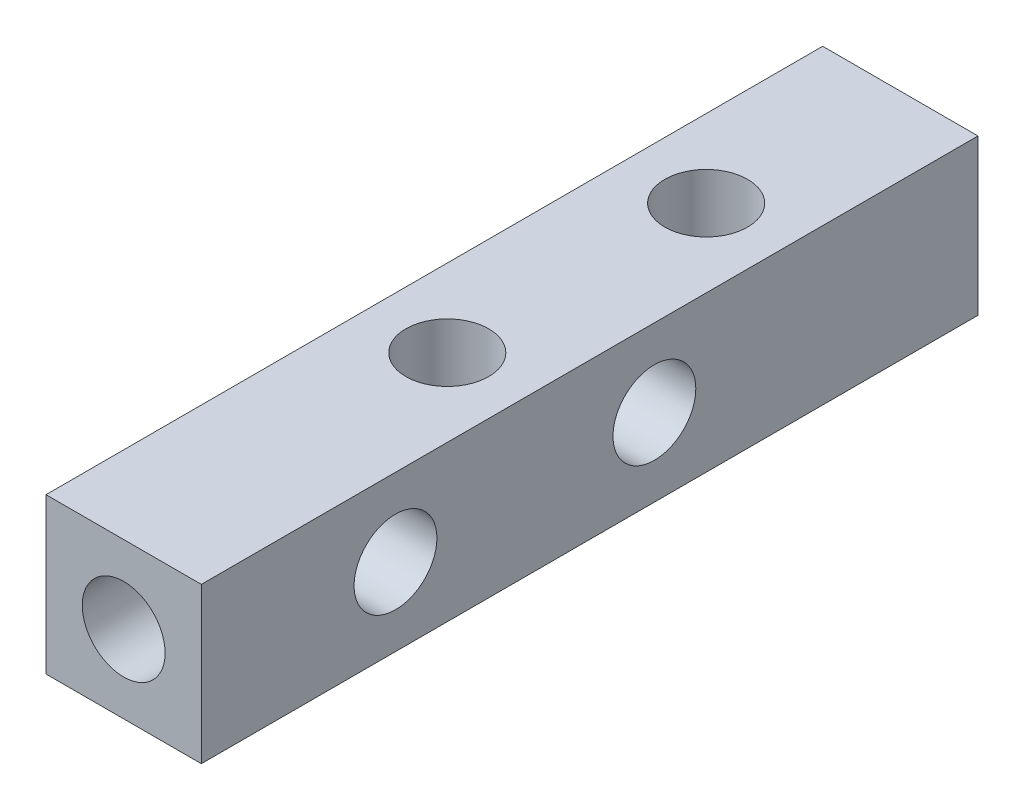
SolidWorks part; units mm, degrees
ref_plane "前视基准面" through (0, 0, 0) normal (0, 0, 1) x (1, 0, 0)
ref_plane "上视基准面" through (0, 0, 0) normal (0, 1, 0) x (1, 0, 0)
ref_plane "右视基准面" through (0, 0, 0) normal (1, 0, 0) x (0, 0, -1)
sketch "草图1" plane through (0, 0, 0) normal (0, 0, 1) x (1, 0, 0)
  line L0 (0, 0) -> (6, 0)
  line L1 (6, 0) -> (6, 6)
  line L2 (6, 6) -> (0, 6)
  line L3 (0, 6) -> (0, 0)
extrude "凸台-拉伸1" add sketch "草图1" along normal blind 30
sketch "草图2" plane through (0, 0, 30) normal (0, 0, 1) x (1, 0, 0)
  circle A0 centre (3, 3) radius 1.6
extrude "切除-拉伸1" cut sketch "草图2" against normal blind 5
extrude "切除-拉伸2" cut sketch "草图2<2>" along normal blind 5 from surface starting at face at (3, 3, 0)
sketch "草图2<2>" plane through (0, 0, 30) normal (0, 0, 1) x (1, 0, 0) same geometry as "草图2"
sketch "草图3" plane through (6, 0, 0) normal (1, 0, 0) x (0, 0, -1)
  circle A0 centre (-22.5, 3) radius 1.6
  circle A1 centre (-12.5, 3) radius 1.6
extrude "切除-拉伸3" cut sketch "草图3" against normal blind 7
sketch "草图4" plane through (0, 6, 0) normal (0, 1, 0) x (1, 0, 0)
  circle A0 centre (3, -7.5) radius 1.6
  circle A1 centre (3, -17.5) radius 1.6
  point P11 (2.7019, -17.5)
extrude "切除-拉伸4" cut sketch "草图4" against normal blind 7
